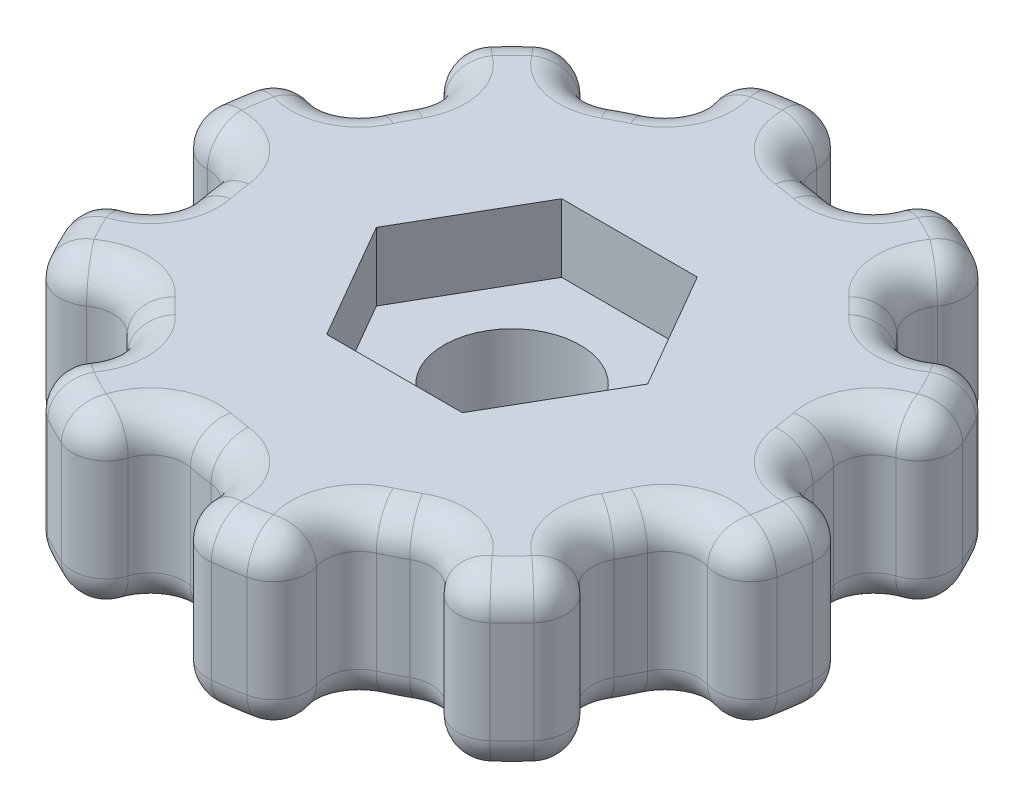
SolidWorks part; units mm, degrees
ref_plane "Front Plane" through (0, 0, 0) normal (0, 0, 1) x (1, 0, 0)
ref_plane "Top Plane" through (0, 0, 0) normal (0, 1, 0) x (1, 0, 0)
ref_plane "Right Plane" through (0, 0, 0) normal (1, 0, 0) x (0, 0, -1)
sketch "Croquis1" plane through (0, 0, 0) normal (0, 1, 0) x (1, 0, 0)
  circle A0 centre (0, 0) radius 10
  dimension "D1" = 20
extrude "Saliente-Extruir1" add sketch "Croquis1" along normal blind 5
sketch "Croquis2" plane through (0, 5, 0) normal (0, 1, 0) x (1, 0, 0)
  line L0 (0, 12.7424) -> (0, 8) construction
  line L1 (0, 8) -> (0, 10)
  line L2 (2.4721, 7.6085) -> (3.0902, 9.5106)
  line L3 (0, 0) -> (0, -12.0258) construction
  line L4 (0, 0) -> (3.0902, 9.5106) construction
  line L5 (4.7023, 6.4721) -> (5.8779, 8.0902)
  line L6 (6.4721, 4.7023) -> (8.0902, 5.8779)
  line L7 (7.6085, 2.4721) -> (9.5106, 3.0902)
  line L8 (8, 0) -> (10, 0)
  line L9 (7.6085, -2.4721) -> (9.5106, -3.0902)
  line L10 (6.4721, -4.7023) -> (8.0902, -5.8779)
  line L11 (4.7023, -6.4721) -> (5.8779, -8.0902)
  line L12 (2.4721, -7.6085) -> (3.0902, -9.5106)
  line L13 (0, -8) -> (0, -10)
  line L14 (-2.4721, -7.6085) -> (-3.0902, -9.5106)
  line L15 (-4.7023, -6.4721) -> (-5.8779, -8.0902)
  line L16 (-6.4721, -4.7023) -> (-8.0902, -5.8779)
  line L17 (-7.6085, -2.4721) -> (-9.5106, -3.0902)
  line L18 (-8, 0) -> (-10, 0)
  line L19 (-7.6085, 2.4721) -> (-9.5106, 3.0902)
  line L20 (-6.4721, 4.7023) -> (-8.0902, 5.8779)
  line L21 (-4.7023, 6.4721) -> (-5.8779, 8.0902)
  line L22 (-2.4721, 7.6085) -> (-3.0902, 9.5106)
  arc A0 (2.4721, 7.6085) -> (0, 8) centre (0, 0) ccw
  arc A1 (3.0902, 9.5106) -> (0, 10) centre (0, 0) ccw
  circle A2 centre (0, 0) radius 10 construction
  arc A3 (8.0902, 5.8779) -> (5.8779, 8.0902) centre (0, 0) ccw
  arc A4 (6.4721, 4.7023) -> (4.7023, 6.4721) centre (0, 0) ccw
  arc A5 (10, 0) -> (9.5106, 3.0902) centre (0, 0) ccw
  arc A6 (8, 0) -> (7.6085, 2.4721) centre (0, 0) ccw
  arc A7 (8.0902, -5.8779) -> (9.5106, -3.0902) centre (0, 0) ccw
  arc A8 (6.4721, -4.7023) -> (7.6085, -2.4721) centre (0, 0) ccw
  arc A9 (3.0902, -9.5106) -> (5.8779, -8.0902) centre (0, 0) ccw
  arc A10 (2.4721, -7.6085) -> (4.7023, -6.4721) centre (0, 0) ccw
  arc A11 (-3.0902, -9.5106) -> (0, -10) centre (0, 0) ccw
  arc A12 (-2.4721, -7.6085) -> (0, -8) centre (0, 0) ccw
  arc A13 (-8.0902, -5.8779) -> (-5.8779, -8.0902) centre (0, 0) ccw
  arc A14 (-6.4721, -4.7023) -> (-4.7023, -6.4721) centre (0, 0) ccw
  arc A15 (-10, 0) -> (-9.5106, -3.0902) centre (0, 0) ccw
  arc A16 (-8, 0) -> (-7.6085, -2.4721) centre (0, 0) ccw
  arc A17 (-8.0902, 5.8779) -> (-9.5106, 3.0902) centre (0, 0) ccw
  arc A18 (-6.4721, 4.7023) -> (-7.6085, 2.4721) centre (0, 0) ccw
  arc A19 (-3.0902, 9.5106) -> (-5.8779, 8.0902) centre (0, 0) ccw
  arc A20 (-2.4721, 7.6085) -> (-4.7023, 6.4721) centre (0, 0) ccw
  point P49 (0, 0)
  dimension "D1" = 2
  dimension "D2" = 18
  dimension "D3" = 10
extrude "Cortar-Extruir1" cut sketch "Croquis2" against normal up to next
fillet "Redondeo1" radius 1 40 edges at (-4.7023, 2.5, -6.4721) (-5.8779, 2.5, -8.0902) (-6.4721, 2.5, -4.7023) (-8.0902, 2.5, -5.8779) (-7.6085, 2.5, -2.4721) (-9.5106, 2.5, -3.0902) (-8, 2.5, 0) (-10, 2.5, 0) (-7.6085, 2.5, 2.4721) (-9.5106, 2.5, 3.0902) (-8.0902, 2.5, 5.8779) (-6.4721, 2.5, 4.7023) (-4.7023, 2.5, 6.4721) (-5.8779, 2.5, 8.0902) (0, 2.5, 8) (-3.0902, 2.5, 9.5106) (-2.4721, 2.5, 7.6085) (0, 2.5, 10) (3.0902, 2.5, 9.5106) (2.4721, 2.5, 7.6085) (4.7023, 2.5, 6.4721) (5.8779, 2.5, 8.0902) (8.0902, 2.5, 5.8779) (7.6085, 2.5, 2.4721) (6.4721, 2.5, 4.7023) (9.5106, 2.5, 3.0902) (10, 2.5, 0) (8, 2.5, 0) (7.6085, 2.5, -2.4721) (9.5106, 2.5, -3.0902) (6.4721, 2.5, -4.7023) (4.7023, 2.5, -6.4721) (5.8779, 2.5, -8.0902) (3.0902, 2.5, -9.5106) (2.4721, 2.5, -7.6085) (0, 2.5, -8) (0, 2.5, -10) (-3.0902, 2.5, -9.5106) (-2.4721, 2.5, -7.6085) (8.0902, 2.5, -5.8779)
fillet "Redondeo2" radius 1 120 edges at (5.4257, 0, -8.035) (5.0715, 0, -6.547) (5.6569, 0, -5.6569) (6.547, 0, -5.0715) (8.035, 0, -5.4257) (8.9101, 0, -4.5399) (9.1124, 0, -3.3113) (7.9512, 0, -2.3157) (7.9015, 0, -1.2515) (8.2776, 0, -0.2546) (9.6896, 0, 0.3333) (9.8769, 0, 1.5643) (9.3184, 0, 2.6772) (7.7938, 0, 2.8001) (7.1281, 0, 3.6319) (6.8464, 0, 4.6594) (7.6431, 0, 5.9651) (7.0711, 0, 7.0711) (5.9651, 0, 7.6431) (4.6594, 0, 6.8464) (3.6319, 0, 7.1281) (2.8001, 0, 7.7938) (2.6772, 0, 9.3184) (1.5643, 0, 9.8769) (0.3333, 0, 9.6896) (-0.2546, 0, 8.2776) (-1.2515, 0, 7.9015) (-2.3157, 0, 7.9512) (-3.3113, 0, 9.1124) (-4.5399, 0, 8.9101) (-5.4257, 0, 8.035) (-5.0715, 0, 6.547) (-5.6569, 0, 5.6569) (-6.547, 0, 5.0715) (-8.035, 0, 5.4257) (-8.9101, 0, 4.5399) (-9.1124, 0, 3.3113) (-7.9512, 0, 2.3157) (-7.9015, 0, 1.2515) (-8.2776, 0, 0.2546) (-9.6896, 0, -0.3333) (-9.8769, 0, -1.5643) (-9.3184, 0, -2.6772) (-7.7938, 0, -2.8001) (-7.1281, 0, -3.6319) (-6.8464, 0, -4.6594) (-7.6431, 0, -5.9651) (-7.0711, 0, -7.0711) (-5.9651, 0, -7.6431) (-4.6594, 0, -6.8464) (-3.6319, 0, -7.1281) (-2.8001, 0, -7.7938) (-2.6772, 0, -9.3184) (-1.5643, 0, -9.8769) (-0.3333, 0, -9.6896) (0.2546, 0, -8.2776) (1.2515, 0, -7.9015) (2.3157, 0, -7.9512) (3.3113, 0, -9.1124) (5.4257, 5, -8.035) (5.0715, 5, -6.547) (5.6569, 5, -5.6569) (6.547, 5, -5.0715) (8.035, 5, -5.4257) (8.9101, 5, -4.5399) (9.1124, 5, -3.3113) (7.9512, 5, -2.3157) (7.9015, 5, -1.2515) (8.2776, 5, -0.2546) (9.6896, 5, 0.3333) (9.8769, 5, 1.5643) (9.3184, 5, 2.6772) (7.7938, 5, 2.8001) (7.1281, 5, 3.6319) (6.8464, 5, 4.6594) (7.6431, 5, 5.9651) (7.0711, 5, 7.0711) (5.9651, 5, 7.6431) (4.6594, 5, 6.8464) (3.6319, 5, 7.1281) (2.8001, 5, 7.7938) (2.6772, 5, 9.3184) (1.5643, 5, 9.8769) (0.3333, 5, 9.6896) (-0.2546, 5, 8.2776) (-1.2515, 5, 7.9015) (-2.3157, 5, 7.9512) (-3.3113, 5, 9.1124) (-4.5399, 5, 8.9101) (-5.4257, 5, 8.035) (-5.0715, 5, 6.547) (-5.6569, 5, 5.6569) (-6.547, 5, 5.0715) (-8.035, 5, 5.4257) (-8.9101, 5, 4.5399) (-9.1124, 5, 3.3113) (-7.9512, 5, 2.3157) (-7.9015, 5, 1.2515) (-8.2776, 5, 0.2546) (-9.6896, 5, -0.3333) (-9.8769, 5, -1.5643) (-9.3184, 5, -2.6772) (-7.7938, 5, -2.8001) (-7.1281, 5, -3.6319) (-6.8464, 5, -4.6594) (-7.6431, 5, -5.9651) (-7.0711, 5, -7.0711) (-5.9651, 5, -7.6431) (-4.6594, 5, -6.8464) (-3.6319, 5, -7.1281) (-2.8001, 5, -7.7938) (-2.6772, 5, -9.3184) (-1.5643, 5, -9.8769) (-0.3333, 5, -9.6896) (0.2546, 5, -8.2776) (1.2515, 5, -7.9015) (2.3157, 5, -7.9512) (3.3113, 5, -9.1124) (4.5399, 0, -8.9101) (4.5399, 5, -8.9101)
sketch "Croquis3" plane through (0, 5, 0) normal (0, 1, 0) x (1, 0, 0)
  line L1 (-1.9919, 3.45) -> (-3.9837, 0)
  line L2 (-3.9837, 0) -> (-1.9919, -3.45)
  line L3 (-1.9919, -3.45) -> (1.9919, -3.45)
  line L4 (1.9919, -3.45) -> (3.9837, 0)
  line L5 (3.9837, 0) -> (1.9919, 3.45)
  line L6 (1.9919, 3.45) -> (-1.9919, 3.45)
  circle A0 centre (0, 0) radius 3.45 construction
  dimension "D1" = 6.9
extrude "Cortar-Extruir2" cut sketch "Croquis3" against normal blind 2
sketch "Croquis4" plane through (0, 5, 0) normal (0, 1, 0) x (1, 0, 0)
  circle A0 centre (0, 0) radius 2
  dimension "D1" = 4
extrude "Cortar-Extruir3" cut sketch "Croquis4" against normal through all
